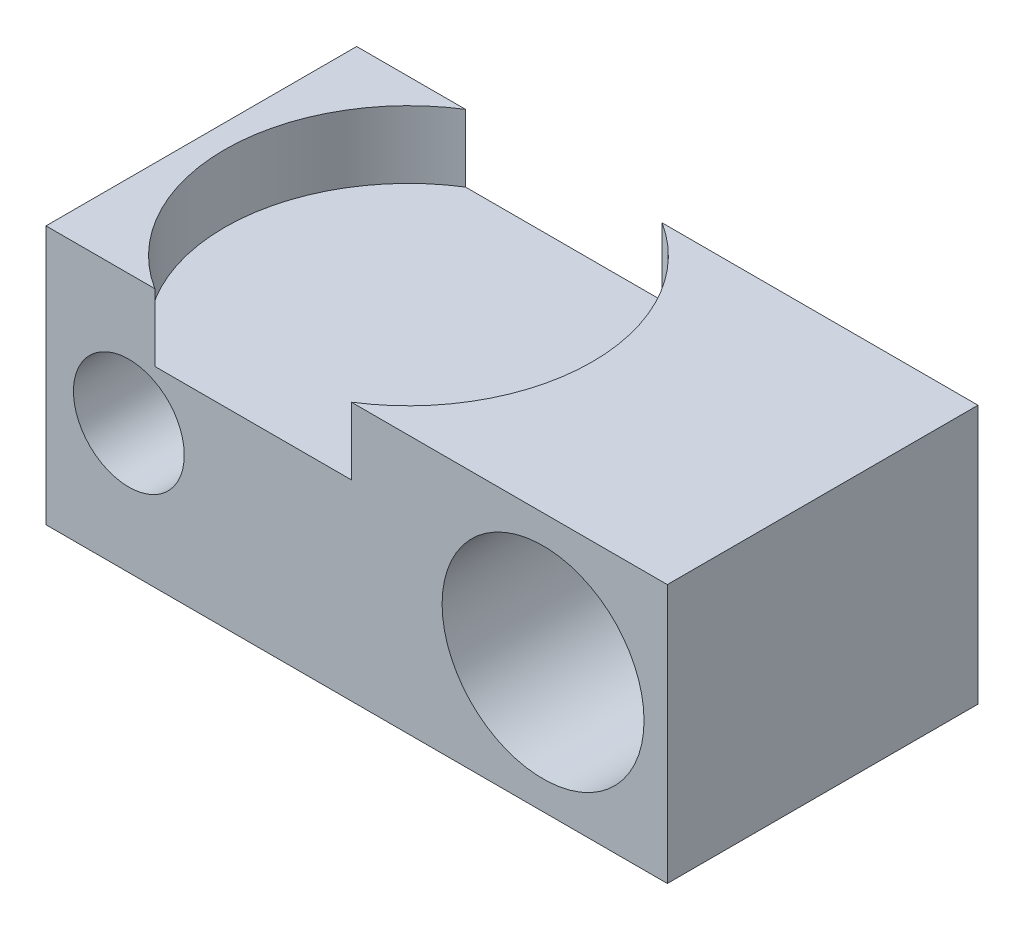
SolidWorks part; units mm, degrees
ref_plane "Front Plane" through (0, 0, 0) normal (0, 0, 1) x (1, 0, 0)
ref_plane "Top Plane" through (0, 0, 0) normal (0, 1, 0) x (1, 0, 0)
ref_plane "Right Plane" through (0, 0, 0) normal (1, 0, 0) x (0, 0, -1)
sketch "Sketch1" plane through (0, 0, 0) normal (0, 0, 1) x (1, 0, 0)
  line L1 (-30, -12.5) -> (30, -12.5)
  line L2 (-30, -12.5) -> (-30, 12.5)
  line L3 (-30, 12.5) -> (30, 12.5)
  line L4 (30, -12.5) -> (30, 12.5)
  line L5 (-30, -12.5) -> (30, 12.5) construction
  line L6 (-30, 12.5) -> (30, -12.5) construction
  circle A0 centre (18, 0) radius 9.75
  circle A1 centre (-22, 0) radius 5.35
  point P0 (0, 0)
  dimension "D2" = 10.7
  dimension "D3" = 19.5
  dimension "D5" = 8
  dimension "D7" = 12.5
  dimension "D1" = 40
  dimension "D4" = 12
  dimension "D6" = 25
  dimension "D8" = 0
extrude "Boss-Extrude1" add sketch "Sketch1" along normal blind 30
sketch "Sketch2" plane through (0, 12.5, 0) normal (0, 1, 0) x (1, 0, 0)
  line L0 (-30, -30) -> (-30, 0) construction
  circle A0 centre (-10, -15) radius 17.75
  line M1 (30, 0) -> (-30, 0)
  line M2 (-30, 0) -> (-30, -30)
  line M3 (-30, -30) -> (30, -30)
  line M4 (30, -30) -> (30, 0)
  dimension "D1" = 20
  dimension "36" = 35.5
extrude "Boss-Extrude2" add sketch "Sketch2" along normal blind 0.0001 contours A0 M1 M2 M3 | A0 M3 M4 M1 region at (17.5486, 12.5, 15) region at (-28.0679, 12.5, 15)
extrude "Cut-Extrude1" cut sketch "Sketch2<3>" against normal blind 6.5
sketch "Sketch2<3>" plane through (0, 12.5, 0) normal (0, 1, 0) x (1, 0, 0) same geometry as "Sketch2"
